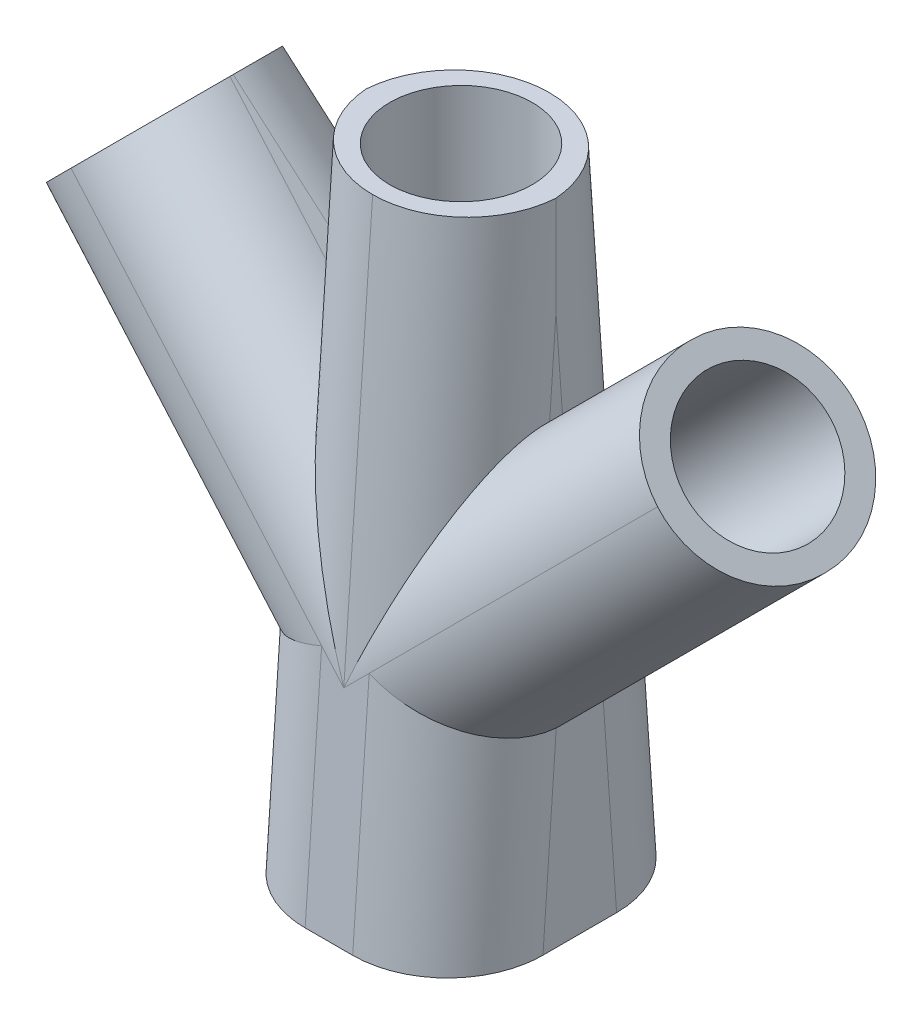
SolidWorks part; units mm, degrees
ref_plane "Спереди" through (0, 0, 0) normal (0, 0, 1) x (1, 0, 0)
ref_plane "Сверху" through (0, 0, 0) normal (0, 1, 0) x (1, 0, 0)
ref_plane "Справа" through (0, 0, 0) normal (1, 0, 0) x (0, 0, -1)
sketch "Эскиз3" plane through (0, 0, 0) normal (0, 0, 1) x (1, 0, 0)
  line L1 (0, -50) -> (0, 50) construction
  line L3 (-6.25, 0) -> (-19.1421, 12.8921)
  line L4 (-19.1421, 12.8921) -> (-12.0711, 19.9632)
  line L5 (-12.0711, 19.9632) -> (-5, 12.8921)
  line L6 (-5, 12.8921) -> (-5, 22.8921)
  line L7 (-5, 22.8921) -> (5, 22.8921)
  line L8 (0, 22.8921) -> (0, 0) construction
  line L9 (5, 12.8921) -> (5, 22.8921)
  line L10 (12.0711, 19.9632) -> (5, 12.8921)
  line L11 (19.1421, 12.8921) -> (12.0711, 19.9632)
  line L12 (6.25, 0) -> (19.1421, 12.8921)
  line L17 (-6.25, 0) -> (-6.25, -10)
  line L18 (-6.25, -10) -> (6.25, -10)
  line L19 (6.25, 0) -> (6.25, -10)
  dimension "D1" = 12.5
  dimension "D2" = 10
  dimension "D3" = 10
  dimension "D4" = 45
  dimension "D5" = 10
extrude "Основа тройника" add sketch "Эскиз3" along normal blind 12.5
sketch "Эскиз4" plane through (0, 22.8921, 0) normal (0, 1, 0) x (-1, 0, 0)
  line L3 (5, 12.5) -> (5, 0) construction
  line L5 (-5, 12.5) -> (5, 12.5) construction
  circle A0 centre (0, 6.25) radius 3.75
  point P2 (0, 0)
  point P4 (0, 4.3932)
  point P5 (0, 0)
  point P7 (0, 0)
  point P8 (5, 6.25)
  point P11 (0, 0)
  point P14 (0, 12.5)
  dimension "D1" = 7.5
extrude "Центральный вырез под гофру" cut sketch "Эскиз4" against normal through all
sketch "Эскиз5" plane through (-16.0171, 16.0171, 0) normal (-0.7071, 0.7071, 0) x (0, 0, 1)
  line L0 (6.25, 16.1872) -> (6.25, -7.0711) construction
  line L1 (12.5, 5.5806) -> (12.5, -4.4194) construction
  circle A0 centre (6.25, 0.5806) radius 3.75
  point P7 (12.5, 0.5806)
  dimension "D1" = 7.5
extrude "Боковой вырез под гофру" cut sketch "Эскиз5" against normal up to next
mirror "Зеркальное отражение1" about plane through (0, 0, 0) normal (1, 0, 0) of "Боковой вырез под гофру"
sketch "Эскиз9" plane through (0, -10, 0) normal (0, -1, 0) x (1, 0, 0)
  circle A0 centre (0, 6.25) radius 5.25
  dimension "D1" = 10.5
extrude "Под толстую гофру" cut sketch "Эскиз9" against normal blind 8
draft "Уклон2" type of draft neutral plane draft angle 4 neutral plane "Сверху" faces to draft 2 face at (0, 9.7733, 0) face at (0, 9.7733, 12.5) neutral plane through (0, 0, 0) neutral plane normal (0, 1, 0) parameters "D1"=4
fillet "Скругление8" radius 5 16 edges at (8.5355, 16.4277, 1.1487) (5, 17.8921, 1.2511) (-5, 17.8921, 1.2511) (-8.5355, 16.4277, 1.1487) (-12.6961, 6.4461, 0.4508) (-6.25, -5, -0.3496) (6.25, -5, -0.3496) (12.6961, 6.4461, 0.4508) (-6.25, -5, 12.8496) (6.25, -5, 12.8496) (12.6961, 6.4461, 12.0492) (8.5355, 16.4277, 11.3513) (5, 17.8921, 11.2489) (-5, 17.8921, 11.2489) (-8.5355, 16.4277, 11.3513) (-12.6961, 6.4461, 12.0492)
